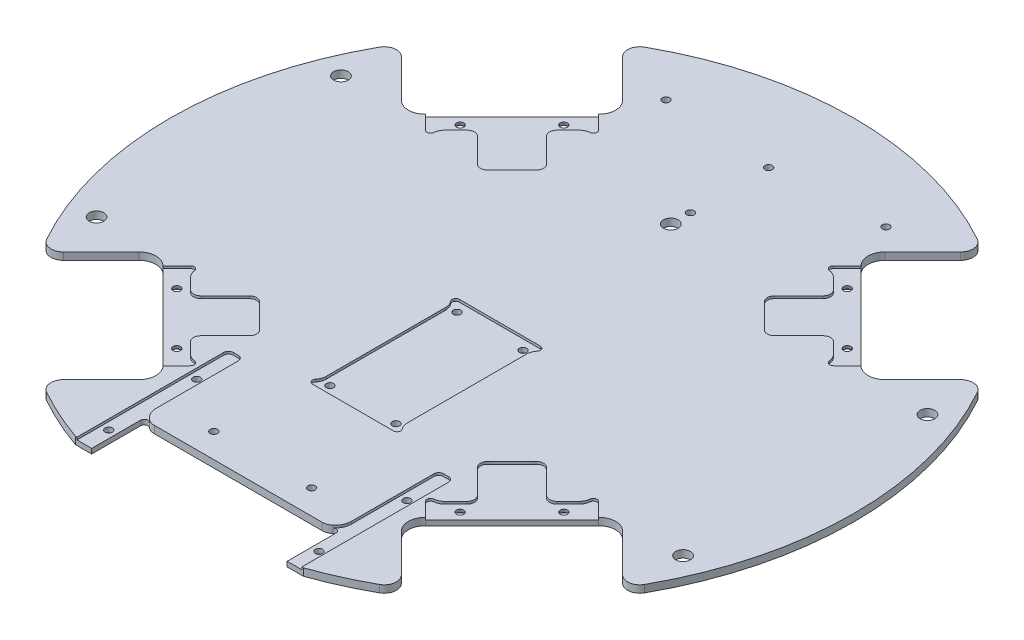
SolidWorks part; units mm, degrees
material "1060 Alloy"
ref_plane "Front Plane" through (0, 0, 0) normal (0, 0, 1) x (1, 0, 0)
ref_plane "Top Plane" through (0, 0, 0) normal (0, 1, 0) x (1, 0, 0)
ref_plane "Right Plane" through (0, 0, 0) normal (1, 0, 0) x (0, 0, -1)
sketch "Sketch1" plane through (0, 0, 0) normal (0, 1, 0) x (1, 0, 0)
  circle A0 centre (0, 0) radius 140
  dimension "D1" = 280
extrude "Boss-Extrude1" add sketch "Sketch1" along normal blind 3
sketch "Sketch7" plane through (0, 3, 0) normal (0, 1, 0) x (1, 0, 0)
  line L0 (-89.1308, -53.7048) -> (-53.7048, -89.1308)
  line L1 (-98.9596, -53.7048) -> (-121.6224, -76.3675)
  line L2 (-53.7048, -98.9596) -> (-76.3675, -121.6224)
  line L3 (-121.6224, -76.3675) -> (-76.3675, -121.6224)
  line L4 (0, 0) -> (-98.9949, -98.9949) construction
  line L7 (0, 0) -> (0, 130) construction
  circle A0 centre (0, 0) radius 140 construction
  arc A1 (-98.9596, -53.7048) -> (-89.1308, -53.7048) centre (-94.0452, -58.6192) cw
  arc A2 (-53.7048, -89.1308) -> (-53.7048, -98.9596) centre (-58.6192, -94.0452) cw
  dimension "D4" = 6.95
  dimension "D1" = 101
  dimension "D2" = 64
  dimension "D3" = 135
extrude "Cut-Extrude4" cut sketch "Sketch7" against normal up to next
sketch "Sketch8" plane through (0, 3, 0) normal (0, 1, 0) x (1, 0, 0)
  line L0 (-89.1308, -53.7048) -> (-53.7048, -89.1308)
  line L1 (-89.1308, -53.7048) -> (-83.474, -48.0479)
  line L2 (-53.7048, -89.1308) -> (-48.0479, -83.474)
  line L3 (-79.4765, -52.0454) -> (-52.0454, -79.4765)
  line L6 (-53.7048, -89.1308) -> (-89.1308, -53.7048) construction
  arc A0 (-83.474, -48.0479) -> (-80.9197, -48.9704) centre (-82.4133, -49.1086) cw
  arc A1 (-80.9197, -48.9704) -> (-79.4765, -52.0454) centre (-75.9409, -48.5099) ccw
  arc A2 (-48.0479, -83.474) -> (-48.9704, -80.9197) centre (-49.1086, -82.4133) ccw
  arc A3 (-48.9704, -80.9197) -> (-52.0454, -79.4765) centre (-48.5099, -75.9409) cw
  dimension "D2" = 1.5
  dimension "D3" = 5
  dimension "D4" = 1.5
  dimension "D5" = 5
  dimension "D1" = 8
extrude "Cut-Extrude5" cut sketch "Sketch8" against normal blind 1
sketch "Sketch14" plane through (0, 3, 0) normal (0, 1, 0) x (1, 0, 0)
  line L0 (-52.0454, -79.4765) -> (-79.4765, -52.0454) construction
  line L1 (-52.0454, -79.4765) -> (-79.4765, -52.0454) construction
  line L2 (-70.7107, -56.5685) -> (-60.8112, -46.669)
  line L3 (-56.5685, -70.7107) -> (-46.669, -60.8112)
  line L4 (-56.5685, -46.669) -> (-46.669, -56.5685)
  line L5 (-74.9533, -56.5685) -> (-56.5685, -74.9533)
  line L8 (-83.474, -48.0479) -> (-89.1308, -53.7048) construction
  arc A0 (-74.9533, -56.5685) -> (-70.7107, -56.5685) centre (-72.832, -54.4472) ccw
  arc A1 (-56.5685, -74.9533) -> (-56.5685, -70.7107) centre (-54.4472, -72.832) cw
  arc A2 (-60.8112, -46.669) -> (-56.5685, -46.669) centre (-58.6899, -48.7904) cw
  arc A3 (-46.669, -60.8112) -> (-46.669, -56.5685) centre (-48.7904, -58.6899) ccw
  dimension "D1" = 3
  dimension "D2" = 20
  dimension "D3" = 20
  dimension "D4" = 15.05
extrude "Cut-Extrude10" cut sketch "Sketch14" against normal up to surface (1 mm away) up to face at (-66.8825, 2, 66.8825)
sketch "Sketch9" plane through (0, 2, 0) normal (0, 1, 0) x (1, 0, 0)
  line L0 (-48.0479, -83.474) -> (-83.474, -48.0479) construction
  line L3 (-48.0479, -83.474) -> (-83.474, -48.0479) construction
  line L4 (-98.9596, -53.7048) -> (-119.0017, -73.7469) construction
  circle A0 centre (-79.196, -57.9828) radius 1.5
  circle A1 centre (-57.9828, -79.196) radius 1.5
  dimension "D4" = 3
  dimension "D1" = 4
  dimension "D2" = 30
  dimension "D3" = 17
  dimension "D5" = 4
extrude "Cut-Extrude6" cut sketch "Sketch9" against normal up to next
fillet "Fillet1" radius 5 2 edges at (-73.7469, 1.5, 119.0017) (-119.0017, 1.5, 73.7469)
pattern_circular "CirPattern1" count 4 over 360 about axis through (0, 3, 0) along (0, 1, 0) of "Cut-Extrude4", "Cut-Extrude6", "Fillet1", "Cut-Extrude5", "Cut-Extrude10"
sketch "Sketch2" plane through (0, 3, 0) normal (0, 1, 0) x (1, 0, 0)
  line L0 (-46.6476, -132) -> (-40, -132)
  line L1 (-40, -132) -> (-40, -112)
  line L2 (-34.3467, -112) -> (34.3467, -112)
  line L3 (40, -112) -> (40, -132)
  line L4 (40, -132) -> (46.6476, -132)
  line L5 (46.6476, -132) -> (46.6476, -140)
  line L6 (46.6476, -140) -> (-46.6476, -140)
  line L7 (-46.6476, -140) -> (-46.6476, -132)
  circle A0 centre (0, 0) radius 140 construction
  arc A1 (-40, -112) -> (-37.5415, -110.8462) centre (-38.5, -112) cw
  arc A2 (-34.3467, -112) -> (-37.5415, -110.8462) centre (-34.3467, -107) cw
  arc A3 (40, -112) -> (37.5415, -110.8462) centre (38.5, -112) ccw
  arc A4 (34.3467, -112) -> (37.5415, -110.8462) centre (34.3467, -107) ccw
  dimension "D5" = 1.5
  dimension "D6" = 5
  dimension "D1" = 8
  dimension "D2" = 20
  dimension "D3" = 80
  dimension "D4" = 6.6476
extrude "Cut-Extrude1" cut sketch "Sketch2" against normal up to next
sketch "Sketch3" plane through (0, 3, 0) normal (0, 1, 0) x (1, 0, 0)
  line L0 (-40, -132) -> (-46.6476, -132) construction
  line L1 (-40, -132) -> (-46, -132)
  line L2 (-40, -132) -> (-40, -72)
  line L3 (-42, -70) -> (-44, -70)
  line L4 (-46, -132) -> (-46, -72)
  line L5 (40, -132) -> (46, -132)
  line L6 (40, -132) -> (40, -72)
  line L7 (42, -70) -> (44, -70)
  line L8 (46, -132) -> (46, -72)
  line L12 (-40, -112) -> (-40, -132) construction
  line L13 (40, -132) -> (40, -112) construction
  arc A0 (40, -72) -> (42, -70) centre (42, -72) cw
  arc A1 (44, -70) -> (46, -72) centre (44, -72) cw
  arc A2 (-40, -72) -> (-42, -70) centre (-42, -72) ccw
  arc A3 (-44, -70) -> (-46, -72) centre (-44, -72) ccw
  dimension "D5" = 2
  dimension "D1" = 6
  dimension "D2" = 62
extrude "Cut-Extrude2" cut sketch "Sketch3" against normal blind 1
sketch "Sketch18" plane through (0, 3, 0) normal (0, 1, 0) x (1, 0, 0)
  line L0 (-40, -112) -> (-40, -72) construction
  line L1 (-40, -112) -> (-40, -72) construction
  line L3 (-40, -105.608) -> (-40, -112)
  line L4 (-40, -112) -> (-37.5415, -110.8462)
  line L5 (40, -72) -> (40, -112) construction
  line L6 (40, -105.608) -> (40, -112)
  line L7 (40, -112) -> (37.5415, -110.8462)
  arc A0 (-37.5415, -110.8462) -> (-40, -105.608) centre (-33.1904, -105.608) cw
  arc A2 (-37.5415, -110.8462) -> (-34.3467, -112) centre (-34.3467, -107) ccw construction
  arc A3 (37.5415, -110.8462) -> (40, -105.608) centre (33.1904, -105.608) ccw
  arc A4 (34.3467, -112) -> (37.5415, -110.8462) centre (34.3467, -107) ccw construction
extrude "Cut-Extrude14" cut sketch "Sketch18" against normal up to surface (1 mm away) up to face at (42.5714, 2, 94.1674)
fillet "Fillet3" radius 1.5 8 edges at (57.9828, 0, 80.696) (79.196, 0, 59.4828) (79.196, 0, -56.4828) (57.9828, 0, -77.696) (-57.9828, 0, -77.696) (-79.196, 0, -56.4828) (-57.9828, 0, 80.696) (-79.196, 0, 59.4828)
sketch "Sketch10" plane through (0, 3, 0) normal (0, 1, 0) x (1, 0, 0)
  circle A0 centre (-13.5, -61) radius 1.5
  circle A1 centre (13.5, -61) radius 1.5
  circle A2 centre (-13.5, -9) radius 1.5
  circle A3 centre (13.5, -9) radius 1.5
  dimension "D3" = 3
  dimension "D1" = 13.5
  dimension "D2" = 27
  dimension "D4" = 61
  dimension "D5" = 52
extrude "Cut-Extrude7" cut sketch "Sketch10" against normal up to next
sketch "Sketch11" plane through (0, 3, 0) normal (0, 1, 0) x (1, 0, 0)
  line L0 (34.3467, -112) -> (-34.3467, -112) construction
  circle A0 centre (-20, -102) radius 1.5
  circle A1 centre (20, -102) radius 1.5
  dimension "D1" = 3
  dimension "D2" = 40
  dimension "D3" = 10
  dimension "D4" = 20
extrude "Cut-Extrude8" cut sketch "Sketch11" against normal up to next
sketch "Sketch13" plane through (0, 3, 0) normal (0, 1, 0) x (1, 0, 0)
  line L0 (-46, -132) -> (-40, -132) construction
  line L4 (-40, -105.608) -> (-40, -72) construction
  line L5 (40, -72) -> (40, -105.608) construction
  circle A0 centre (-43, -86) radius 1.5
  circle A1 centre (-43, -122) radius 1.5
  circle A2 centre (43, -122) radius 1.5
  circle A3 centre (43, -86) radius 1.5
  dimension "D1" = 3
  dimension "D2" = 10
  dimension "D3" = 36
  dimension "D4" = 3
  dimension "D5" = 3
extrude "Cut-Extrude9" cut sketch "Sketch13" against normal up to next
sketch "Sketch15" plane through (0, 3, 0) normal (0, 1, 0) x (1, 0, 0)
  line L1 (-16.55, -4.95) -> (16.55, -4.95)
  line L2 (-16.55, -10.6033) -> (-16.55, -59.3967)
  line L3 (-16.55, -65.05) -> (16.55, -65.05)
  line L4 (16.55, -10.6033) -> (16.55, -59.3967)
  circle A0 centre (-13.5, -61) radius 1.5 construction
  circle A1 centre (-13.5, -9) radius 1.5 construction
  arc A2 (-16.55, -4.95) -> (-17.7038, -7.4085) centre (-16.55, -6.45) ccw
  arc A3 (-16.55, -10.6033) -> (-17.7038, -7.4085) centre (-21.55, -10.6033) ccw
  arc A4 (16.55, -4.95) -> (17.7038, -7.4085) centre (16.55, -6.45) cw
  arc A5 (17.7038, -7.4085) -> (16.55, -10.6033) centre (21.55, -10.6033) ccw
  arc A6 (-16.55, -65.05) -> (-17.7038, -62.5915) centre (-16.55, -63.55) cw
  arc A7 (-17.7038, -62.5915) -> (-16.55, -59.3967) centre (-21.55, -59.3967) ccw
  arc A8 (16.55, -65.05) -> (17.7038, -62.5915) centre (16.55, -63.55) ccw
  arc A9 (17.7038, -62.5915) -> (16.55, -59.3967) centre (21.55, -59.3967) cw
  dimension "D3" = 4.05
  dimension "D5" = 1.5
  dimension "D6" = 5
  dimension "D1" = 33.1
  dimension "D2" = 4.05
  dimension "D4" = 16.55
extrude "Cut-Extrude11" cut sketch "Sketch15" against normal blind 1
sketch "Sketch16" plane through (0, 3, 0) normal (0, 1, 0) x (1, 0, 0)
  circle A0 centre (0, 73) radius 1.5
  circle A1 centre (-45, 108) radius 1.5
  circle A2 centre (45, 108) radius 1.5
  circle A3 centre (0, 105) radius 1.5
  circle A4 centre (0, 65) radius 3
  dimension "D2" = 3
  dimension "D5" = 6
  dimension "D1" = 73
  dimension "D3" = 108
  dimension "D4" = 90
  dimension "D6" = 32
  dimension "D7" = 65
extrude "Cut-Extrude12" cut sketch "Sketch16" against normal up to next
sketch "Sketch17" plane through (0, 3, 0) normal (0, 1, 0) x (1, 0, 0)
  circle A0 centre (-120, 50) radius 3
  circle A1 centre (-120, -50) radius 3
  circle A2 centre (120, 50) radius 3
  circle A3 centre (120, -50) radius 3
  dimension "D1" = 6
  dimension "D2" = 50
  dimension "D3" = 50
  dimension "D4" = 120
  dimension "D5" = 120
extrude "Cut-Extrude13" cut sketch "Sketch17" against normal up to next
